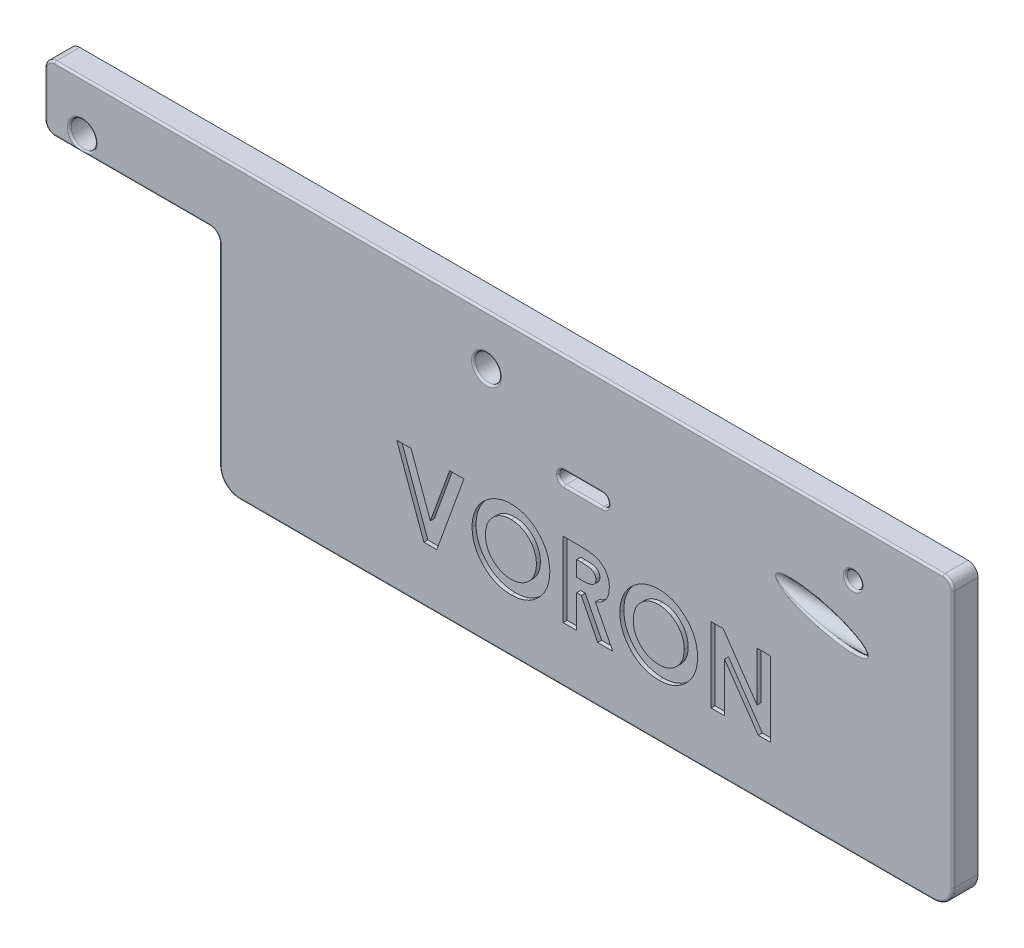
SolidWorks part; units mm, degrees
ref_plane "Front Plane" through (0, 0, 0) normal (0, 0, 1) x (1, 0, 0)
ref_plane "Top Plane" through (0, 0, 0) normal (0, 1, 0) x (1, 0, 0)
ref_plane "Right Plane" through (0, 0, 0) normal (1, 0, 0) x (0, 0, -1)
sketch "Sketch1" plane through (0, 0, 0) normal (0, 0, 1) x (1, 0, 0)
  line L1 (0, 0) -> (182, 0)
  line L2 (0, 0) -> (0, -13)
  line L3 (0, -13) -> (182, -13)
  line L4 (182, 0) -> (182, -13)
  dimension "D1" = 13
  dimension "D2" = 182
extrude "Boss-Extrude1" add sketch "Sketch1" along normal blind 5
sketch "Sketch2" plane through (0, 0, 5) normal (0, 0, 1) x (1, 0, 0)
  line L1 (182, -13) -> (35, -13)
  line L2 (182, -13) -> (182, -57.5)
  line L3 (182, -57.5) -> (35, -57.5)
  line L4 (35, -13) -> (35, -57.5)
  dimension "D1" = 44.5
  dimension "D2" = 147
extrude "Boss-Extrude2" add sketch "Sketch2" against normal blind 5
sketch "Sketch3" plane through (0, 0, 5) normal (0, 0, 1) x (1, 0, 0)
  line L0 (182, 0) -> (0, 0) construction
  line L1 (0, 0) -> (0, -13) construction
  circle A0 centre (88.5, -10) radius 2.6
  circle A1 centre (7.5, -10) radius 2.6
  dimension "D1" = 5.2
  dimension "D2" = 5.2
  dimension "D3" = 10
  dimension "D4" = 10
  dimension "D5" = 81
  dimension "D6" = 7.5
extrude "Cut-Extrude1" cut sketch "Sketch3" against normal blind 5
sketch "Sketch4" plane through (0, 0, 5) normal (0, 0, 1) x (1, 0, 0)
  line L0 (182, 0) -> (0, 0) construction
  line L1 (182, -57.5) -> (182, 0) construction
  circle A0 centre (162, -10) radius 1.6
  dimension "D1" = 3.2
  dimension "D2" = 10
  dimension "D3" = 20
extrude "Cut-Extrude2" cut sketch "Sketch4" against normal through all
fillet "Fillet1" radius 2 4 edges at (35, -13, 2.5) (182, 0, 2.5) (0, 0, 2.5) (0, -13, 2.5)
fillet "Fillet2" radius 4 2 edges at (182, -57.5, 2.5) (35, -57.5, 2.5)
sketch "Sketch5" plane through (0, 0, 5) normal (0, 0, 1) x (1, 0, 0)
  line L0 (89.5, 5) -> (182, -20) construction
  line L1 (182, -53.5) -> (182, -2) construction
  line L2 (180, 0) -> (2, 0) construction
  line L3 (182, -20) -> (175.27, -44.9008) construction
  circle A1 centre (88.5, -10) radius 2.6 construction
  dimension "D1" = 20
  dimension "D2" = 5
  dimension "D3" = 1
  dimension "D4" = 90
ref_axis "Axis1" through (182, -20, 5) along (-0.2609, -0.9654, 0)
ref_plane "Plane1" through (161.7422, -43.7141, -44.8936) normal (-0.9325, 0.252, 0.2588) x (-0.2609, -0.9654, 0)
sketch "Sketch6" plane through (161.7422, -43.7141, -44.8936) normal (-0.9325, 0.252, 0.2588) x (-0.2609, -0.9654, 0)
  line L0 (-28.1782, 51.6537) -> (-2.3839, 51.6537) construction
  line L2 (-47.0329, 49.9385) -> (-47.0329, 45.1089) construction
  circle A0 centre (-22.0329, 44.6537) radius 2.1
  dimension "D1" = 4.2
  dimension "D3" = 25
  dimension "D2" = 7
extrude "Cut-Extrude3" cut sketch "Sketch6" against normal through all both and the other way through all
sketch "Sketch7" plane through (0, 0, 5) normal (0, 0, 1) x (1, 0, 0)
  line L0 (180, 0) -> (2, 0) construction
  line L1 (102.9, -20) -> (112.9, -20)
  line L2 (102.9, -20) -> (102.9, -22.5)
  line L3 (102.9, -22.5) -> (112.9, -22.5)
  line L4 (112.9, -20) -> (112.9, -22.5)
  line L5 (182, -53.5) -> (182, -2) construction
  dimension "D1" = 2.5
  dimension "D2" = 10
  dimension "D3" = 20
  dimension "D4" = 69.1
extrude "Cut-Extrude4" cut sketch "Sketch7" against normal through all
fillet "Fillet3" radius 1.2 4 edges at (112.9, -20, 2.5) (112.9, -22.5, 2.5) (102.9, -22.5, 2.5) (102.9, -20, 2.5)
sketch "Sketch8" plane through (0, 0, 5) normal (0, 0, 1) x (1, 0, 0)
  text T0 "VORON" font "Century Gothic" height 15
extrude "Cut-Extrude5" cut sketch "Sketch8" against normal blind 0.8
fillet "Fillet4" radius 0.4 24 edges at (181.4142, -0.5858, 5) (182, -27.75, 5) (180.8284, -56.3284, 5) (108.5, -57.5, 5) (36.1716, -56.3284, 5) (35, -34.25, 5) (34.4142, -13.5858, 5) (17.5, -13, 5) (0.5858, -12.4142, 5) (0, -6.5, 5) (0.5858, -0.5858, 5) (112.5485, -20.3515, 5) (112.9, -21.25, 5) (112.5485, -22.1485, 5) (107.9, -22.5, 5) (103.2515, -22.1485, 5) (102.9, -21.25, 5) (103.2515, -20.3515, 5) (91, 0, 5) (163.6, -10, 5) (146.4548, -16.7589, 5) (107.9, -20, 5) (91.1, -10, 5) (10.1, -10, 5)
equation "\"D2@Sketch2\"=\"D2@Sketch1\"-35"
equation "\"D6@Sketch3\"=96/2-\"D5@Sketch3\"/2"
equation "\"D2@Sketch1\"=147+35"
equation "\"D1@Sketch2\"=7+37.5"
equation "\"D4@Sketch7\"=\"D2@Sketch2\"/2-4.4"
